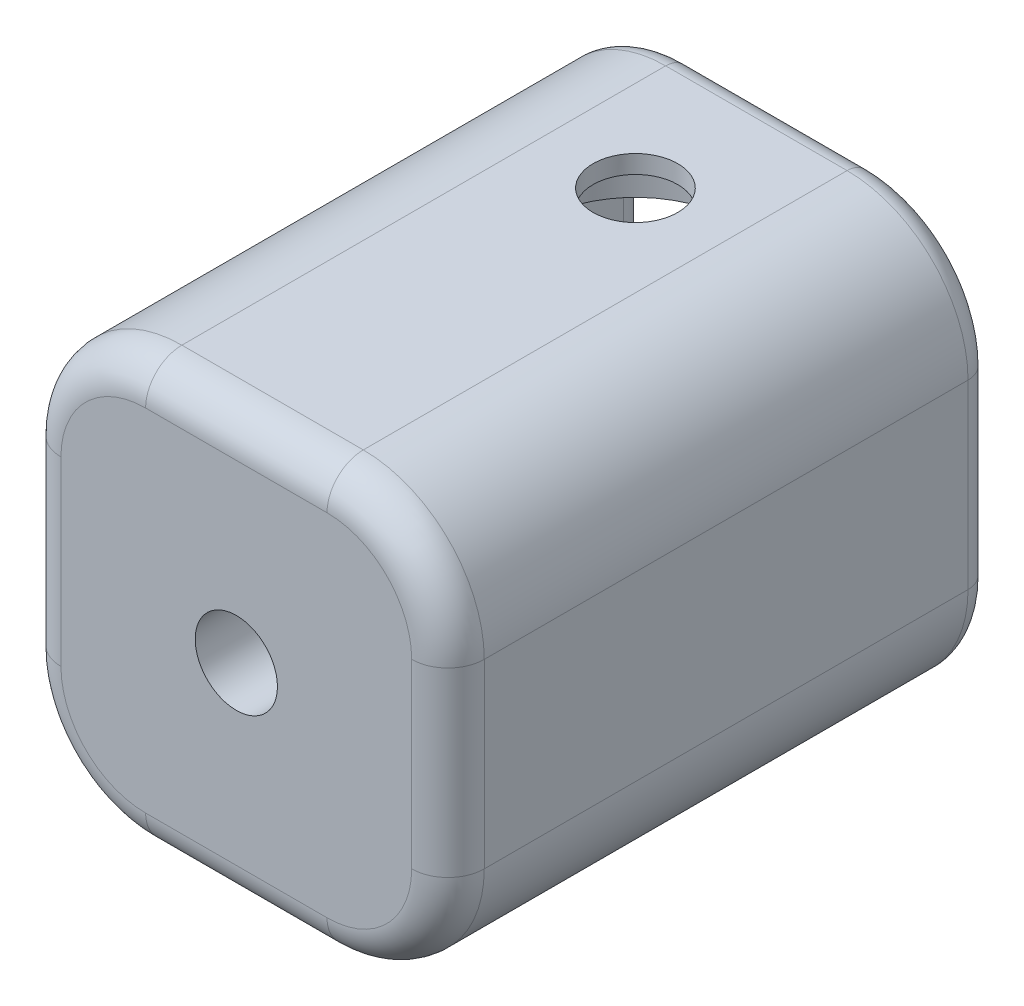
SolidWorks part; units mm, degrees
ref_plane "Front Plane" through (0, 0, 0) normal (0, 0, 1) x (1, 0, 0)
ref_plane "Top Plane" through (0, 0, 0) normal (0, 1, 0) x (1, 0, 0)
ref_plane "Right Plane" through (0, 0, 0) normal (1, 0, 0) x (0, 0, -1)
sketch "Sketch1" plane through (0, 0, 0) normal (0, 0, 1) x (1, 0, 0)
  line L1 (-11, 11) -> (11, 11)
  line L2 (-11, 11) -> (-11, -11)
  line L3 (-11, -11) -> (11, -11)
  line L4 (11, 11) -> (11, -11)
  line L5 (-11, 11) -> (11, -11) construction
  line L6 (-11, -11) -> (11, 11) construction
  line L7 (-17.5, 17.5) -> (17.5, 17.5)
  line L8 (-17.5, 17.5) -> (-17.5, -17.5)
  line L9 (-17.5, -17.5) -> (17.5, -17.5)
  line L10 (17.5, 17.5) -> (17.5, -17.5)
  line L11 (-17.5, 17.5) -> (17.5, -17.5) construction
  line L12 (-17.5, -17.5) -> (17.5, 17.5) construction
  point P0 (0, 0)
  point P6 (0, 0)
  dimension "D1" = 22
  dimension "D2" = 22
  dimension "D3" = 35
  dimension "D4" = 35
extrude "Boss-Extrude1" add sketch "Sketch1" along normal blind 30
ref_plane "Plane1" through (0, 0, 0) normal (0, 1, 0) x (1, 0, 0)
sketch "Sketch3" plane through (0, 17.5, 0) normal (0, 1, 0) x (1, 0, 0)
  line L0 (0, 0) -> (0, -30) construction
  line L1 (17.5, 0) -> (-17.5, 0) construction
  line L2 (17.5, -30) -> (-17.5, -30) construction
  circle A0 centre (0, -12) radius 3.5
  dimension "D1" = 7
  dimension "D2" = 12
extrude "Cut-Extrude2" cut sketch "Sketch3" against normal through all
sketch "Sketch4" plane through (0, -11, 0) normal (0, 1, 0) x (1, 0, 0)
  circle A0 centre (0, -12) radius 8.25
  dimension "D1" = 16.5
extrude "Cut-Extrude3" cut sketch "Sketch4" against normal blind 5
mirror "Mirror2" about plane through (0, 0, 0) normal (0, 1, 0) of "Cut-Extrude3"
fillet "Fillet1" radius 10 4 edges at (17.5, 17.5, 15) (17.5, -17.5, 15) (-17.5, -17.5, 15) (-17.5, 17.5, 15)
fillet "Fillet4" radius 2 8 edges at (14.5711, 14.5711, 0) (17.5, 0, 0) (14.5711, -14.5711, 0) (0, -17.5, 0) (-14.5711, -14.5711, 0) (-17.5, 0, 0) (-14.5711, 14.5711, 0) (0, 17.5, 0)
fillet "Fillet5" radius 3 4 edges at (-11, 11, 15) (11, 11, 15) (11, -11, 15) (-11, -11, 15)
sketch "Sketch6" plane through (0, 0, 30) normal (0, 0, 1) x (1, 0, 0)
  line L1 (7.5, 17.5) -> (-7.5, 17.5)
  line L2 (17.5, 7.5) -> (17.5, -7.5)
  line L3 (7.5, -17.5) -> (-7.5, -17.5)
  line L4 (-17.5, 7.5) -> (-17.5, -7.5)
  line L5 (17.5, 17.5) -> (-17.5, -17.5) construction
  line L6 (17.5, -17.5) -> (-17.5, 17.5) construction
  arc A0 (-7.5, -17.5) -> (-17.5, -7.5) centre (-7.5, -7.5) cw
  arc A1 (17.5, -7.5) -> (7.5, -17.5) centre (7.5, -7.5) cw
  arc A2 (7.5, 17.5) -> (17.5, 7.5) centre (7.5, 7.5) cw
  arc A3 (-7.5, 17.5) -> (-17.5, 7.5) centre (-7.5, 7.5) ccw
  point P0 (0, 0)
  dimension "D3" = 10
  dimension "D1" = 35
  dimension "D2" = 35
extrude "Nut Retention Area" add sketch "Sketch6" along normal blind 15
sketch "Sketch7" plane through (0, 0, 45) normal (0, 0, 1) x (1, 0, 0)
  circle A0 centre (0, 0) radius 3.4
  dimension "D1" = 6.8
sketch "Sketch8" plane through (0, 0, 30) normal (0, 0, -1) x (-1, 0, 0)
  line L1 (3.2332, -5.6) -> (6.4663, 0)
  line L2 (6.4663, 0) -> (3.2332, 5.6)
  line L3 (3.2332, 5.6) -> (-3.2332, 5.6)
  line L4 (-3.2332, 5.6) -> (-6.4663, 0)
  line L5 (-6.4663, 0) -> (-3.2332, -5.6)
  line L6 (-3.2332, -5.6) -> (3.2332, -5.6)
  circle A0 centre (0, 0) radius 5.6 construction
  dimension "D1" = 11.2
extrude "Cut-Extrude5" cut sketch "Sketch8" against normal blind 8 contours L3 L4 L5 L6 L1 L2
sketch "Sketch9" plane through (0, 0, 30) normal (0, 0, -1) x (-1, 0, 0)
  circle A0 centre (0, 0) radius 8.5
  dimension "D1" = 17
extrude "Nut Captivator" [suppressed] add sketch "Sketch9" against normal blind 2.3 contours A0
extrude "Cut-Extrude6" cut sketch "Sketch7" against normal through all contours A0
fillet "Fillet6" radius 3 8 edges at (0, 17.5, 45) (14.5711, 14.5711, 45) (17.5, 0, 45) (14.5711, -14.5711, 45) (0, -17.5, 45) (-14.5711, -14.5711, 45) (-17.5, 0, 45) (-14.5711, 14.5711, 45)
fillet "Fillet7" radius 2 8 edges at (10.1213, 10.1213, 0) (11, 0, 0) (10.1213, -10.1213, 0) (0, -11, 0) (-10.1213, -10.1213, 0) (-11, 0, 0) (-10.1213, 10.1213, 0) (0, 11, 0)
move or copy body "Body-Move/Copy1" [suppressed] bodies to move or copy 111
equation "\"Core_Height\"= 35"
equation "\"D3@Sketch1\"=\"Core_Height\""
